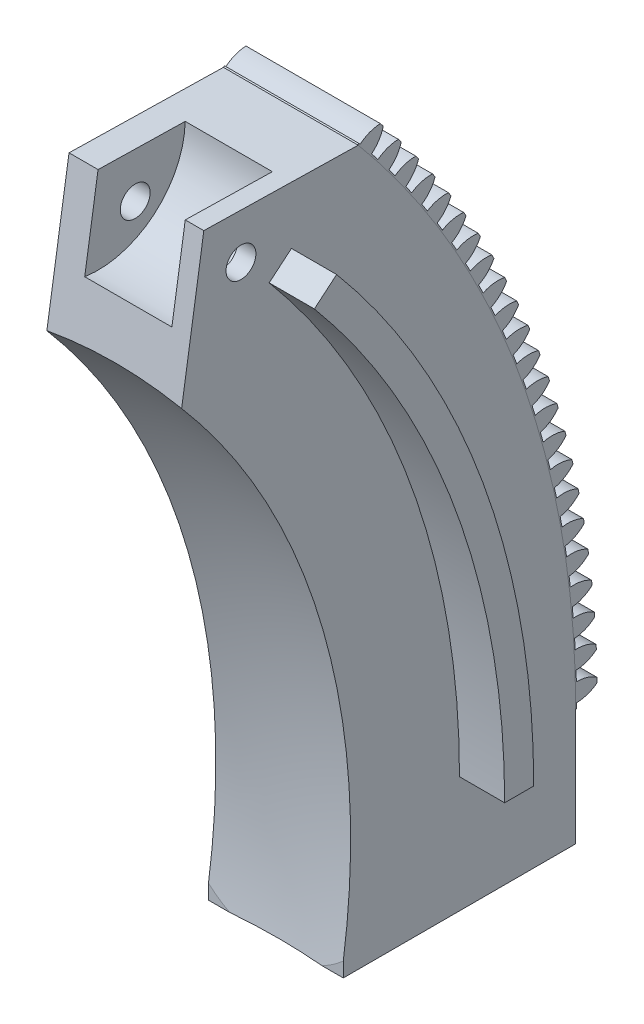
SolidWorks part; units mm, degrees
material "ABS"
ref_plane "Front Plane" through (0, 0, 0) normal (0, 0, 1) x (1, 0, 0)
ref_plane "Top Plane" through (0, 0, 0) normal (0, 1, 0) x (1, 0, 0)
ref_plane "Right Plane" through (0, 0, 0) normal (1, 0, 0) x (0, 0, -1)
ref_plane "Plane2" through (6.35, 0, 0) normal (1, 0, 0) x (0, 0, -1)
sketch "Sketch1" plane through (0, 0, 0) normal (1, 0, 0) x (0, 0, -1)
  line L0 (-1000, 0) -> (152.4, 0) construction
  line L1 (152.4, 0) -> (152.4, -25.4)
  line L2 (0, 0) -> (116.7452, 97.9608) construction
  line L4 (203.2, 0) -> (49000, 0) construction
  line L7 (152.4, -25.4) -> (203.2, -25.4)
  line L8 (203.2, 0) -> (203.2, -25.4)
  line L10 (-19.9245, -15.6845) -> (159.6649, 125.6875) construction
  line L61 (160.8976, 124.1056) -> (0, 0) construction
  line L62 (136.2027, 114.2876) -> (121.9167, 131.313) construction
  line L63 (116.7452, 97.9608) -> (121.9167, 131.313)
  line L67 (121.9167, 131.313) -> (155.6602, 130.6144)
  line L68 (0, 0) -> (35966.99, 34732.9185) construction
  line L69 (159.6736, 125.6943) -> (159.6985, 125.714) construction
  arc A2 (152.4, 0) -> (116.7452, 97.9608) centre (0, 0) ccw
  circle A19 centre (0, 0) radius 203.2 construction
  arc A22 (155.6602, 130.6144) -> (203.2, 0) centre (0, 0) cw
  point P6 (159.6985, 125.714)
  point P7 (116.7452, 97.9608)
  dimension "D1" = 152.4
  dimension "D2" = 6.35
  dimension "D12" = 406.4
  dimension "D3" = 40
  dimension "D4" = 50.8
  dimension "D5" = 25.4
  dimension "D11" = 22.225
  dimension "D13" = 44
sketch "Sketch2" plane through (6.35, 0, 0) normal (1, 0, 0) x (0, 0, -1)
  line L0 (0, 0) -> (165.1, 0) construction
  line L1 (165.1, 0) -> (190.5, 0) construction
  line L2 (0, 0) -> (49240.3877, 8682.4089) construction
  circle A0 centre (165.1, 0) radius 3.2639
  circle A1 centre (190.5, 0) radius 3.2639
  arc A3 (165.1, 0) -> (162.5918, 28.6693) centre (0, 0) ccw construction
  circle A4 centre (162.5918, 28.6693) radius 3.2639
  arc A5 (190.5, 0) -> (187.6059, 33.08) centre (0, 0) ccw construction
  circle A6 centre (187.6059, 33.08) radius 3.2639
  dimension "D3" = 6.5278
  dimension "D4" = 6.5278
  dimension "D6" = 6.5278
  dimension "D7" = 6.5278
  dimension "D1" = 165.1
  dimension "D2" = 25.4
  dimension "D5" = 10
sketch "Sketch11" plane through (6.35, 0, 0) normal (1, 0, 0) x (0, 0, -1)
  line L0 (-785.502, -659.1144) -> (0, 0) construction
  line L2 (-1000, 0) -> (0, 0) construction
  line L3 (203.2, 0) -> (208, 0)
  line L4 (155.6602, 130.6144) -> (159.3372, 133.6998)
  line L5 (159.3372, 133.6998) -> (921.7047, 773.4021) construction
  arc A0 (-230, 0) -> (-176.1902, -147.8412) centre (0, 0) ccw construction
  arc A1 (-208, 0) -> (-159.3372, -133.6998) centre (0, 0) ccw construction
  arc A2 (-205.6, 0) -> (-157.4987, -132.1571) centre (0, 0) ccw construction
  arc A3 (208, 0) -> (159.3372, 133.6998) centre (0, 0) ccw
  arc A4 (230, 0) -> (176.1902, 147.8412) centre (0, 0) ccw construction
  arc A5 (-205.6, 0) -> (-157.4987, -132.1571) centre (0, 0) ccw
  arc A6 (155.6602, 130.6144) -> (203.2, 0) centre (0, 0) cw
  dimension "D1" = 460
  dimension "D2" = 416
  dimension "D4" = 203.2
  dimension "D3" = 2.4
  dimension "D5" = 40
extrude "Boss-Extrude2" add sketch "Sketch11" against normal blind 6.35 contours L3 A3 L4 region at (6.35, 69.9896, -192.2947)
sketch "Sketch12" plane through (6.35, 0, 0) normal (1, 0, 0) x (0, 0, -1)
  line L0 (0, 0) -> (208, 0) construction
  line L1 (203.2, 0) -> (208, 0) construction
  line L2 (205.994, 1.5708) -> (205.994, -1.5708) construction
  line L3 (0, 0) -> (203.4969, 1.1234) construction
  line L4 (201.6783, 0) -> (208.9831, 2.6587) construction
  line L5 (0, 0) -> (208.9757, 3.1872) construction
  line L6 (205.994, 1.5708) -> (205.9461, 4.712) construction
  circle A0 centre (0, 0) radius 206 construction
  arc A1 (208, 0) -> (159.3372, 133.6998) centre (0, 0) ccw construction
  circle A2 centre (0, 0) radius 203.5 construction
  arc A3 (203.4969, 1.1234) -> (208.9694, 3.5771) centre (203.4559, 8.5441) ccw
  arc A4 (209, 0) -> (208.9694, -3.5771) centre (0, 0) cw
  arc A5 (203.4969, -1.1234) -> (208.9694, -3.5771) centre (203.4559, -8.5441) cw
  arc A6 (209, 0) -> (160.1033, 134.3426) centre (0, 0) ccw
  arc A7 (209, 0) -> (208.9694, 3.5771) centre (0, 0) ccw
  arc A8 (203.4969, 1.1234) -> (203.4969, -1.1234) centre (0, 0) cw
  arc A9 (208, 0) -> (159.3372, 133.6998) centre (0, 0) ccw construction
  dimension "D1" = 412
  dimension "D3" = 20
  dimension "D4" = 0.874
  dimension "D5" = 4.5
  dimension "D2" = 1
extrude "Boss-Extrude3" add sketch "Sketch1" along normal blind 29.464
extrude "Cut-Extrude4" cut sketch "Sketch12" against normal blind 6.35
pattern_circular "CirPattern3" count 100 every 1.748 about axis through (0, 0, 0) along (1, 0, 0) of "Cut-Extrude4"
sketch "Sketch15" plane through (6.35, 0, 0) normal (1, 0, 0) x (0, 0, -1)
  line L0 (0, 0) -> (130.0347, 121.2593) construction
  line L1 (-196961.5506, -34729.6355) -> (246201.9383, 43412.0444) construction
  circle A0 centre (130.0347, 121.2593) radius 3.2639
  dimension "D3" = 6.5278
  dimension "D1" = 177.8
  dimension "D2" = 33
extrude "Cut-Extrude7" cut sketch "Sketch15" against normal through all both and the other way through all
sketch "Sketch21" plane through (0, 0, 0) normal (0, 1, 0) x (1, 0, 0)
  line L0 (0, 0) -> (-11.1125, 0) construction
  line L1 (12.7, 0) -> (12.7, 152.4) construction
  line L2 (0, 0) -> (12.7, 0) construction
  line L3 (-11.1125, 0) -> (-11.1125, 38.1) construction
  line L4 (-11.1125, 38.1) -> (-127.8666, 38.1) construction
  line L5 (-11.1125, 38.1) -> (105.6416, 38.1) construction
  line L6 (107.5153, 38.1) -> (-49892.4847, 38.1) construction
  line L7 (-1000, 0) -> (49000, 0) construction
  line L8 (14.732, 38.1) -> (14.732, 152.4) construction
  line L9 (29.464, 152.4) -> (0, 152.4) construction
  line L10 (-76.1776, 38.1) -> (157.3306, 38.1) construction
  line L11 (29.464, 152.4) -> (0, 152.4) construction
  line L12 (0, 152.4) -> (14.732, 152.4) construction
  line L13 (14.732, 152.4) -> (14.732, 130.0627) construction
  line L15 (-76.1776, 38.1) -> (-102.108, 38.1)
  line L16 (105.6416, 38.1) -> (131.572, 38.1)
  line L17 (-76.1776, 38.1) -> (105.6416, 38.1)
  arc A0 (105.6416, 38.1) -> (-127.8666, 38.1) centre (-11.1125, 38.1) ccw construction
  arc A1 (-76.1776, 38.1) -> (157.3306, 38.1) centre (40.5765, 38.1) cw construction
  arc A2 (-102.108, 38.1) -> (131.572, 38.1) centre (14.732, 38.1) cw
  dimension "D3" = 12.7
  dimension "D5" = 116.84
  dimension "D1" = 11.1125
  dimension "D2" = 152.4
  dimension "D4" = 38.1
revolve "Cut-Revolve7" cut sketch "Sketch21" angle 360 about L7 reverse direction yes
sketch "Sketch22" plane through (6.35, 0, 0) normal (1, 0, 0) x (0, 0, -1)
  line L0 (0, 0) -> (130.0347, 121.2593)
  line L1 (0, 0) -> (177.8, 0)
  dimension "D1" = 177.8
sketch "Sketch23" plane through (0, 0, 0) normal (1, 0, 0) x (0, 0, -1)
  line L0 (0, 0) -> (152.4, 0) construction
  line L1 (0, 0) -> (116.7452, 97.9608) construction
  line L2 (152.4, 0) -> (171.45, 0) construction
  line L3 (116.7452, 97.9608) -> (136.2027, 114.2876) construction
  line L4 (177.8, 0) -> (184.15, 0)
  line L5 (136.2027, 114.2876) -> (141.0671, 118.3693)
  arc A0 (152.4, 0) -> (116.7452, 97.9608) centre (0, 0) ccw construction
  circle A2 centre (171.45, 0) radius 6.35 construction
  arc A3 (177.8, 0) -> (136.2027, 114.2876) centre (0, 0) ccw
  arc A4 (184.15, 0) -> (141.0671, 118.3693) centre (0, 0) ccw
  circle A5 centre (190.5, 0) radius 6.35 construction
  dimension "D4" = 6.35
  dimension "D5" = 12.7
  dimension "D6" = 12.7
  dimension "D1" = 152.4
  dimension "D2" = 40
  dimension "D3" = 19.05
extrude "Boss-Extrude4" add sketch "Sketch23" against normal blind 9.8742
ref_plane "Plane3" through (14.732, 0, 0) normal (1, 0, 0) x (0, 0, -1)
mirror "Mirror2" about plane through (14.732, 0, 0) normal (1, 0, 0) of "Boss-Extrude4"
sketch "Sketch24" plane through (0, -15.3774, -99.171) normal (0, 0.1532, 0.9882) x (1, 0, 0)
  line L0 (0, 148.4434) -> (6.35, 148.4434) construction
  line L1 (29.464, 148.4434) -> (0, 148.4434) construction
  line L3 (6.35, 148.4434) -> (25.4, 148.4434)
  line L4 (6.35, 148.4434) -> (6.35, 129.3934)
  line L5 (6.35, 129.3934) -> (25.4, 129.3934)
  line L6 (25.4, 148.4434) -> (25.4, 129.3934)
  dimension "D1" = 6.35
  dimension "D2" = 19.05
  dimension "D3" = 19.05
revolve "Cut-Revolve8" cut sketch "Sketch24" angle 360 about L0
sketch "Sketch25" plane through (0, 0, -203.2) normal (0, 0, -1) x (-1, 0, 0)
  line L0 (0, 0) -> (0, -3.175) construction
  line L1 (0, -25.4) -> (0, 0) construction
  line L3 (0, -3.175) -> (-6.35, -3.175)
  line L4 (0, -3.175) -> (0, -9.525)
  line L5 (0, -9.525) -> (-6.35, -9.525)
  line L6 (-6.35, -3.175) -> (-6.35, -9.525)
  dimension "D1" = 3.175
  dimension "D2" = 6.35
  dimension "D3" = 6.35
extrude "Boss-Extrude5" add sketch "Sketch25" along normal blind 4.7625
fillet "Fillet3" radius 2.54 3 edges at (3.175, -9.525, -203.2) (3.175, -3.175, -203.2) (6.35, -6.35, -203.2)
sketch "Sketch26" plane through (0, 0, 0) normal (-1, 0, 0) x (0, 0, 1)
  circle A0 centre (0, 0) radius 206
  dimension "D1" = 412
sketch "Sketch27" plane through (6.35, 0, 0) normal (1, 0, 0) x (0, 0, -1)
  line L2 (155.89, 130.8073) -> (155.6602, 130.6144)
  line L3 (203.2, 0) -> (203.5, 0)
  line L4 (155.89, 130.8073) -> (155.6602, 130.6144)
  line L5 (203.2, 0) -> (203.5, 0)
  arc A94 (203.368, 7.3287) -> (207.805, 9.0055) centre (203.1007, 14.7447) ccw
  arc A95 (207.805, 9.0055) -> (207.7585, 10.0204) centre (0, 0) ccw
  arc A96 (207.7585, 10.0204) -> (203.1869, 11.2847) centre (203.5984, 3.8753) ccw
  arc A97 (203.1869, 11.2847) -> (203.0499, 13.5273) centre (0, 0) ccw
  arc A98 (203.0499, 13.5273) -> (207.4337, 15.3385) centre (202.5566, 20.9317) ccw
  arc A99 (207.4337, 15.3385) -> (207.3563, 16.3516) centre (0, 0) ccw
  arc A100 (207.3563, 16.3516) -> (202.7482, 17.4759) centre (203.3855, 10.0825) ccw
  arc A101 (202.7482, 17.4759) -> (202.5429, 19.7132) centre (0, 0) ccw
  arc A102 (202.5429, 19.7132) -> (206.8694, 21.6573) centre (201.8241, 27.0991) ccw
  arc A103 (206.8694, 21.6573) -> (206.7612, 22.6675) centre (0, 0) ccw
  arc A104 (206.7612, 22.6675) -> (202.121, 23.6508) centre (202.9834, 16.2802) ccw
  arc A105 (202.121, 23.6508) -> (201.8476, 25.8808) centre (0, 0) ccw
  arc A106 (201.8476, 25.8808) -> (206.1127, 27.956) centre (200.9038, 33.2414) ccw
  arc A107 (206.1127, 27.956) -> (205.9737, 28.9624) centre (0, 0) ccw
  arc A108 (205.9737, 28.9624) -> (201.3057, 29.8037) centre (202.3925, 22.4629) ccw
  arc A109 (201.3057, 29.8037) -> (200.9644, 32.0244) centre (0, 0) ccw
  arc A110 (200.9644, 32.0244) -> (205.1643, 34.2286) centre (199.7966, 39.3527) ccw
  arc A111 (205.1643, 34.2286) -> (204.9947, 35.2304) centre (0, 0) ccw
  arc A112 (204.9947, 35.2304) -> (200.3032, 35.9289) centre (201.6134, 28.6246) ccw
  arc A113 (200.3032, 35.9289) -> (199.8943, 38.1381) centre (0, 0) ccw
  arc A114 (199.8943, 38.1381) -> (204.0251, 40.4694) centre (198.5036, 45.4275) ccw
  arc A115 (204.0251, 40.4694) -> (203.825, 41.4655) centre (0, 0) ccw
  arc A116 (203.825, 41.4655) -> (199.1143, 42.0207) centre (200.6467, 34.7598) ccw
  arc A117 (199.1143, 42.0207) -> (198.6383, 44.2164) centre (0, 0) ccw
  arc A118 (198.6383, 44.2164) -> (202.696, 46.6726) centre (197.0259, 51.4599) ccw
  arc A119 (202.696, 46.6726) -> (202.4656, 47.6621) centre (0, 0) ccw
  arc A120 (202.4656, 47.6621) -> (197.7402, 48.0734) centre (199.4933, 40.8625) ccw
  arc A121 (197.7402, 48.0734) -> (197.1975, 50.2535) centre (0, 0) ccw
  arc A122 (197.1975, 50.2535) -> (201.1784, 52.8323) centre (195.3649, 57.4445) ccw
  arc A123 (201.1784, 52.8323) -> (200.9179, 53.8144) centre (0, 0) ccw
  arc A124 (200.9179, 53.8144) -> (196.1822, 54.0813) centre (198.1544, 46.9273) ccw
  arc A125 (196.1822, 54.0813) -> (195.5732, 56.2439) centre (0, 0) ccw
  arc A126 (195.5732, 56.2439) -> (199.4736, 58.9429) centre (193.5222, 63.3757) ccw
  arc A127 (199.4736, 58.9429) -> (199.1834, 59.9166) centre (0, 0) ccw
  arc A128 (199.1834, 59.9166) -> (194.4417, 60.039) centre (196.6311, 52.9484) ccw
  arc A129 (194.4417, 60.039) -> (193.767, 62.182) centre (0, 0) ccw
  arc A130 (193.767, 62.182) -> (197.5833, 64.9987) centre (191.4995, 69.2479) ccw
  arc A131 (197.5833, 64.9987) -> (197.2635, 65.963) centre (0, 0) ccw
  arc A132 (197.2635, 65.963) -> (192.5203, 65.9408) centre (194.9249, 58.9203) ccw
  arc A133 (192.5203, 65.9408) -> (191.7806, 68.0622) centre (0, 0) ccw
  arc A134 (191.7806, 68.0622) -> (195.5092, 70.994) centre (189.2986, 75.0557) ccw
  arc A135 (195.5092, 70.994) -> (195.1601, 71.9481) centre (0, 0) ccw
  arc A136 (195.1601, 71.9481) -> (190.4198, 71.7812) centre (193.0374, 64.8374) ccw
  arc A137 (190.4198, 71.7812) -> (189.6157, 73.8791) centre (0, 0) ccw
  arc A138 (189.6157, 73.8791) -> (193.2532, 76.9233) centre (186.9217, 80.7937) ccw
  arc A139 (193.2532, 76.9233) -> (192.8752, 77.8663) centre (0, 0) ccw
  arc A140 (192.8752, 77.8663) -> (188.1422, 77.5549) centre (190.9703, 70.6941) ccw
  arc A141 (188.1422, 77.5549) -> (187.2745, 79.6273) centre (0, 0) ccw
  arc A142 (187.2745, 79.6273) -> (190.8175, 82.781) centre (184.3708, 86.4565) ccw
  arc A143 (190.8175, 82.781) -> (190.4109, 83.712) centre (0, 0) ccw
  arc A144 (190.4109, 83.712) -> (185.6896, 83.2565) centre (188.7256, 76.4851) ccw
  arc A145 (185.6896, 83.2565) -> (184.7591, 85.3014) centre (0, 0) ccw
  arc A146 (184.7591, 85.3014) -> (188.2042, 88.5617) centre (181.6485, 92.0389) ccw
  arc A147 (188.2042, 88.5617) -> (187.7694, 89.4799) centre (0, 0) ccw
  arc A148 (187.7694, 89.4799) -> (183.0642, 88.8806) centre (186.3053, 82.2049) ccw
  arc A149 (183.0642, 88.8806) -> (182.0718, 90.8962) centre (0, 0) ccw
  arc A150 (182.0718, 90.8962) -> (185.4159, 94.26) centre (178.7571, 97.5357) ccw
  arc A151 (185.4159, 94.26) -> (184.9533, 95.1645) centre (0, 0) ccw
  arc A152 (184.9533, 95.1645) -> (180.2685, 94.422) centre (183.7117, 87.8483) ccw
  arc A153 (180.2685, 94.422) -> (179.2151, 96.4064) centre (0, 0) ccw
  arc A154 (179.2151, 96.4064) -> (182.4551, 99.8706) centre (175.6995, 102.9417) ccw
  arc A155 (182.4551, 99.8706) -> (181.9651, 100.7606) centre (0, 0) ccw
  arc A156 (181.9651, 100.7606) -> (177.3052, 99.8756) centre (180.9472, 93.4099) ccw
  arc A157 (177.3052, 99.8756) -> (176.1917, 101.827) centre (0, 0) ccw
  arc A158 (176.1917, 101.827) -> (179.3246, 105.3884) centre (172.4785, 108.252) ccw
  arc A159 (179.3246, 105.3884) -> (178.8076, 106.263) centre (0, 0) ccw
  arc A160 (178.8076, 106.263) -> (174.1769, 105.2362) centre (178.0144, 98.8847) ccw
  arc A161 (174.1769, 105.2362) -> (173.0044, 107.1528) centre (0, 0) ccw
  arc A162 (173.0044, 107.1528) -> (176.0272, 110.8081) centre (169.097, 113.4616) ccw
  arc A163 (176.0272, 110.8081) -> (175.4839, 111.6665) centre (0, 0) ccw
  arc A164 (175.4839, 111.6665) -> (170.8866, 110.499) centre (174.916, 104.2675) ccw
  arc A165 (170.8866, 110.499) -> (169.6562, 112.3789) centre (0, 0) ccw
  arc A166 (169.6562, 112.3789) -> (172.5661, 116.1247) centre (165.5582, 118.5656) ccw
  arc A167 (172.5661, 116.1247) -> (171.9968, 116.9662) centre (0, 0) ccw
  arc A168 (171.9968, 116.9662) -> (167.4373, 115.659) centre (171.6549, 109.5532) ccw
  arc A169 (167.4373, 115.659) -> (166.1502, 117.5005) centre (0, 0) ccw
  arc A170 (166.1502, 117.5005) -> (168.9445, 121.3333) centre (161.8654, 123.5593) ccw
  arc A171 (168.9445, 121.3333) -> (168.3498, 122.157) centre (0, 0) ccw
  arc A172 (168.3498, 122.157) -> (163.8323, 120.7114) centre (168.2341, 114.7371) ccw
  arc A173 (163.8323, 120.7114) -> (162.4896, 122.5128) centre (0, 0) ccw
  arc A174 (162.4896, 122.5128) -> (165.1657, 126.429) centre (158.022, 128.4382) ccw
  arc A175 (165.1657, 126.429) -> (164.5462, 127.2342) centre (0, 0) ccw
  arc A176 (164.5462, 127.2342) -> (160.0748, 125.6515) centre (164.6568, 119.8142) ccw
  arc A177 (160.0748, 125.6515) -> (158.6778, 127.4111) centre (0, 0) ccw
  arc A178 (158.6778, 127.4111) -> (161.2333, 131.4071) centre (154.0317, 133.1975) ccw
  arc A179 (161.2333, 131.4071) -> (160.5895, 132.1931) centre (0, 0) ccw
  arc A180 (160.5895, 132.1931) -> (156.1685, 130.4747) centre (160.9264, 124.7799) ccw
  arc A181 (156.1685, 130.4747) -> (155.89, 130.8073) centre (0, 0) ccw
  arc A182 (203.2, 0) -> (155.6602, 130.6144) centre (0, 0) ccw
  arc A183 (203.5, 0) -> (203.4969, 1.1234) centre (0, 0) ccw
  arc A184 (203.4969, 1.1234) -> (207.9829, 2.664) centre (203.4559, 8.5441) ccw
  arc A185 (207.9829, 2.664) -> (207.9675, 3.6799) centre (0, 0) ccw
  arc A186 (207.9675, 3.6799) -> (203.4365, 5.083) centre (203.6219, -2.3355) ccw
  arc A187 (203.4365, 5.083) -> (203.368, 7.3287) centre (0, 0) ccw
  arc A188 (203.368, 7.3287) -> (207.805, 9.0055) centre (203.1007, 14.7447) ccw
  arc A189 (207.805, 9.0055) -> (207.7585, 10.0204) centre (0, 0) ccw
  arc A190 (207.7585, 10.0204) -> (203.1869, 11.2847) centre (203.5984, 3.8753) ccw
  arc A191 (203.1869, 11.2847) -> (203.0499, 13.5273) centre (0, 0) ccw
  arc A192 (203.0499, 13.5273) -> (207.4337, 15.3385) centre (202.5566, 20.9317) ccw
  arc A193 (207.4337, 15.3385) -> (207.3563, 16.3516) centre (0, 0) ccw
  arc A194 (207.3563, 16.3516) -> (202.7482, 17.4759) centre (203.3855, 10.0825) ccw
  arc A195 (202.7482, 17.4759) -> (202.5429, 19.7132) centre (0, 0) ccw
  arc A196 (202.5429, 19.7132) -> (206.8694, 21.6573) centre (201.8241, 27.0991) ccw
  arc A197 (206.8694, 21.6573) -> (206.7612, 22.6675) centre (0, 0) ccw
  arc A198 (206.7612, 22.6675) -> (202.121, 23.6508) centre (202.9834, 16.2802) ccw
  arc A199 (202.121, 23.6508) -> (201.8476, 25.8808) centre (0, 0) ccw
  arc A200 (201.8476, 25.8808) -> (206.1127, 27.956) centre (200.9038, 33.2414) ccw
  arc A201 (206.1127, 27.956) -> (205.9737, 28.9624) centre (0, 0) ccw
  arc A202 (205.9737, 28.9624) -> (201.3057, 29.8037) centre (202.3925, 22.4629) ccw
  arc A203 (201.3057, 29.8037) -> (200.9644, 32.0244) centre (0, 0) ccw
  arc A204 (200.9644, 32.0244) -> (205.1643, 34.2286) centre (199.7966, 39.3527) ccw
  arc A205 (205.1643, 34.2286) -> (204.9947, 35.2304) centre (0, 0) ccw
  arc A206 (204.9947, 35.2304) -> (200.3032, 35.9289) centre (201.6134, 28.6246) ccw
  arc A207 (200.3032, 35.9289) -> (199.8943, 38.1381) centre (0, 0) ccw
  arc A208 (199.8943, 38.1381) -> (204.0251, 40.4694) centre (198.5036, 45.4275) ccw
  arc A209 (204.0251, 40.4694) -> (203.825, 41.4655) centre (0, 0) ccw
  arc A210 (203.825, 41.4655) -> (199.1143, 42.0207) centre (200.6467, 34.7598) ccw
  arc A211 (199.1143, 42.0207) -> (198.6383, 44.2164) centre (0, 0) ccw
  arc A212 (198.6383, 44.2164) -> (202.696, 46.6726) centre (197.0259, 51.4599) ccw
  arc A213 (202.696, 46.6726) -> (202.4656, 47.6621) centre (0, 0) ccw
  arc A214 (202.4656, 47.6621) -> (197.7402, 48.0734) centre (199.4933, 40.8625) ccw
  arc A215 (197.7402, 48.0734) -> (197.1975, 50.2535) centre (0, 0) ccw
  arc A216 (197.1975, 50.2535) -> (201.1784, 52.8323) centre (195.3649, 57.4445) ccw
  arc A217 (201.1784, 52.8323) -> (200.9179, 53.8144) centre (0, 0) ccw
  arc A218 (200.9179, 53.8144) -> (196.1822, 54.0813) centre (198.1544, 46.9273) ccw
  arc A219 (196.1822, 54.0813) -> (195.5732, 56.2439) centre (0, 0) ccw
  arc A220 (195.5732, 56.2439) -> (199.4736, 58.9429) centre (193.5222, 63.3757) ccw
  arc A221 (199.4736, 58.9429) -> (199.1834, 59.9166) centre (0, 0) ccw
  arc A222 (199.1834, 59.9166) -> (194.4417, 60.039) centre (196.6311, 52.9484) ccw
  arc A223 (194.4417, 60.039) -> (193.767, 62.182) centre (0, 0) ccw
  arc A224 (193.767, 62.182) -> (197.5833, 64.9987) centre (191.4995, 69.2479) ccw
  arc A225 (197.5833, 64.9987) -> (197.2635, 65.963) centre (0, 0) ccw
  arc A226 (197.2635, 65.963) -> (192.5203, 65.9408) centre (194.9249, 58.9203) ccw
  arc A227 (192.5203, 65.9408) -> (191.7806, 68.0622) centre (0, 0) ccw
  arc A228 (191.7806, 68.0622) -> (195.5092, 70.994) centre (189.2986, 75.0557) ccw
  arc A229 (195.5092, 70.994) -> (195.1601, 71.9481) centre (0, 0) ccw
  arc A230 (195.1601, 71.9481) -> (190.4198, 71.7812) centre (193.0374, 64.8374) ccw
  arc A231 (190.4198, 71.7812) -> (189.6157, 73.8791) centre (0, 0) ccw
  arc A232 (189.6157, 73.8791) -> (193.2532, 76.9233) centre (186.9217, 80.7937) ccw
  arc A233 (193.2532, 76.9233) -> (192.8752, 77.8663) centre (0, 0) ccw
  arc A234 (192.8752, 77.8663) -> (188.1422, 77.5549) centre (190.9703, 70.6941) ccw
  arc A235 (188.1422, 77.5549) -> (187.2745, 79.6273) centre (0, 0) ccw
  arc A236 (187.2745, 79.6273) -> (190.8175, 82.781) centre (184.3708, 86.4565) ccw
  arc A237 (190.8175, 82.781) -> (190.4109, 83.712) centre (0, 0) ccw
  arc A238 (190.4109, 83.712) -> (185.6896, 83.2565) centre (188.7256, 76.4851) ccw
  arc A239 (185.6896, 83.2565) -> (184.7591, 85.3014) centre (0, 0) ccw
  arc A240 (184.7591, 85.3014) -> (188.2042, 88.5617) centre (181.6485, 92.0389) ccw
  arc A241 (188.2042, 88.5617) -> (187.7694, 89.4799) centre (0, 0) ccw
  arc A242 (187.7694, 89.4799) -> (183.0642, 88.8806) centre (186.3053, 82.2049) ccw
  arc A243 (183.0642, 88.8806) -> (182.0718, 90.8962) centre (0, 0) ccw
  arc A244 (182.0718, 90.8962) -> (185.4159, 94.26) centre (178.7571, 97.5357) ccw
  arc A245 (185.4159, 94.26) -> (184.9533, 95.1645) centre (0, 0) ccw
  arc A246 (184.9533, 95.1645) -> (180.2685, 94.422) centre (183.7117, 87.8483) ccw
  arc A247 (180.2685, 94.422) -> (179.2151, 96.4064) centre (0, 0) ccw
  arc A248 (179.2151, 96.4064) -> (182.4551, 99.8706) centre (175.6995, 102.9417) ccw
  arc A249 (182.4551, 99.8706) -> (181.9651, 100.7606) centre (0, 0) ccw
  arc A250 (181.9651, 100.7606) -> (177.3052, 99.8756) centre (180.9472, 93.4099) ccw
  arc A251 (177.3052, 99.8756) -> (176.1917, 101.827) centre (0, 0) ccw
  arc A252 (176.1917, 101.827) -> (179.3246, 105.3884) centre (172.4785, 108.252) ccw
  arc A253 (179.3246, 105.3884) -> (178.8076, 106.263) centre (0, 0) ccw
  arc A254 (178.8076, 106.263) -> (174.1769, 105.2362) centre (178.0144, 98.8847) ccw
  arc A255 (174.1769, 105.2362) -> (173.0044, 107.1528) centre (0, 0) ccw
  arc A256 (173.0044, 107.1528) -> (176.0272, 110.8081) centre (169.097, 113.4616) ccw
  arc A257 (176.0272, 110.8081) -> (175.4839, 111.6665) centre (0, 0) ccw
  arc A258 (175.4839, 111.6665) -> (170.8866, 110.499) centre (174.916, 104.2675) ccw
  arc A259 (170.8866, 110.499) -> (169.6562, 112.3789) centre (0, 0) ccw
  arc A260 (169.6562, 112.3789) -> (172.5661, 116.1247) centre (165.5582, 118.5656) ccw
  arc A261 (172.5661, 116.1247) -> (171.9968, 116.9662) centre (0, 0) ccw
  arc A262 (171.9968, 116.9662) -> (167.4373, 115.659) centre (171.6549, 109.5532) ccw
  arc A263 (167.4373, 115.659) -> (166.1502, 117.5005) centre (0, 0) ccw
  arc A264 (166.1502, 117.5005) -> (168.9445, 121.3333) centre (161.8654, 123.5593) ccw
  arc A265 (168.9445, 121.3333) -> (168.3498, 122.157) centre (0, 0) ccw
  arc A266 (168.3498, 122.157) -> (163.8323, 120.7114) centre (168.2341, 114.7371) ccw
  arc A267 (163.8323, 120.7114) -> (162.4896, 122.5128) centre (0, 0) ccw
  arc A268 (162.4896, 122.5128) -> (165.1657, 126.429) centre (158.022, 128.4382) ccw
  arc A269 (165.1657, 126.429) -> (164.5462, 127.2342) centre (0, 0) ccw
  arc A270 (164.5462, 127.2342) -> (160.0748, 125.6515) centre (164.6568, 119.8142) ccw
  arc A271 (160.0748, 125.6515) -> (158.6778, 127.4111) centre (0, 0) ccw
  arc A272 (158.6778, 127.4111) -> (161.2333, 131.4071) centre (154.0317, 133.1975) ccw
  arc A273 (161.2333, 131.4071) -> (160.5895, 132.1931) centre (0, 0) ccw
  arc A274 (160.5895, 132.1931) -> (156.1685, 130.4747) centre (160.9264, 124.7799) ccw
  arc A275 (156.1685, 130.4747) -> (155.89, 130.8073) centre (0, 0) ccw
  arc A276 (203.2, 0) -> (155.6602, 130.6144) centre (0, 0) ccw
  arc A277 (203.5, 0) -> (203.4969, 1.1234) centre (0, 0) ccw
  arc A278 (203.4969, 1.1234) -> (207.9829, 2.664) centre (203.4559, 8.5441) ccw
  arc A279 (207.9829, 2.664) -> (207.9675, 3.6799) centre (0, 0) ccw
  arc A280 (207.9675, 3.6799) -> (203.4365, 5.083) centre (203.6219, -2.3355) ccw
  arc A281 (203.4365, 5.083) -> (203.368, 7.3287) centre (0, 0) ccw
  dimension "D1" = 0
extrude "Boss-Extrude6" add sketch "Sketch27" along normal blind 23.0187
equation "\"Module\"= 2mm"
equation "\"Number of Teeth\"= 206"
equation "\"D1@Sketch12\"=\"Module\" * \"Number of Teeth\""
equation "\"D4@Sketch12\"=180 / \"Number of Teeth\""
equation "\"D2\"= 360 / \"Number of Teeth\""
equation "\"D2@Sketch11\"=( \"Number of Teeth\" + 2) * \"Module\""
equation "\"D2@CirPattern3\"= 360 / \"Number of Teeth\""
equation "\"D5@Sketch12\"= 2.25 * \"Module\""
equation "\"D1@Sketch26\"= \"Module\" * \"Number of Teeth\""
